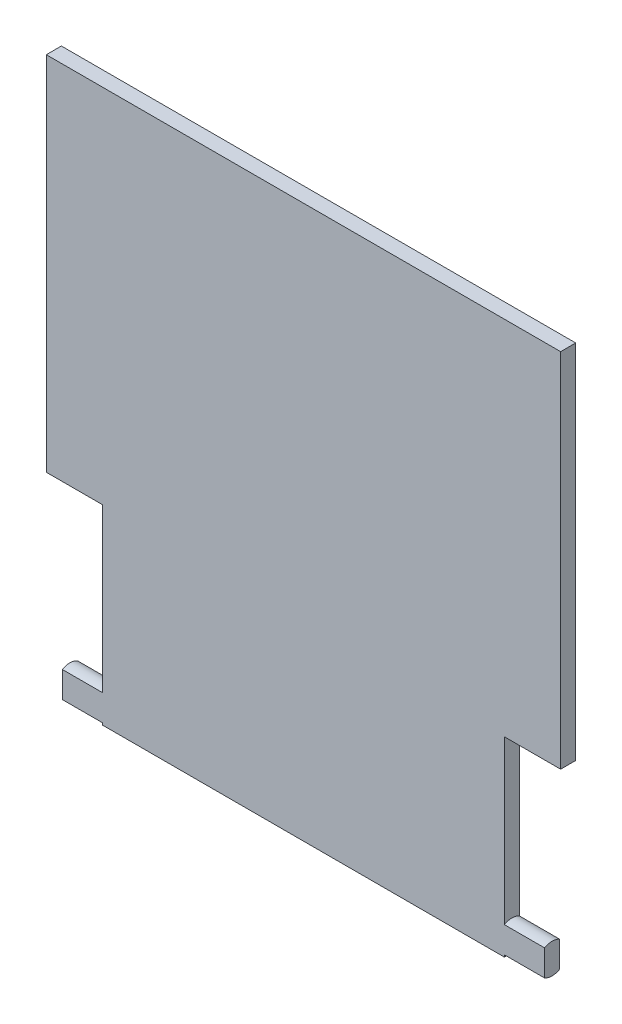
SolidWorks part; units mm, degrees
ref_plane "Front Plane" through (0, 0, 0) normal (0, 0, 1) x (1, 0, 0)
ref_plane "Top Plane" through (0, 0, 0) normal (0, 1, 0) x (1, 0, 0)
ref_plane "Right Plane" through (0, 0, 0) normal (1, 0, 0) x (0, 0, -1)
sketch "Sketch1" plane through (0, 0, 0) normal (0, 0, 1) x (1, 0, 0)
  line L0 (12, 0) -> (-12, 0)
  line L1 (-12, 0) -> (-12, 1.5)
  line L2 (-12, 1.5) -> (-10, 1.5)
  line L3 (-10, 1.5) -> (-10, 9.5)
  line L4 (-10, 9.5) -> (-12.8, 9.5)
  line L5 (-12.8, 9.5) -> (-12.8, 27.5)
  line L6 (-12.8, 27.5) -> (12.8, 27.5)
  line L7 (0, 2.4918) -> (0, -0.4688) construction
  line L8 (12.8, 9.5) -> (12.8, 27.5)
  line L9 (10, 9.5) -> (12.8, 9.5)
  line L10 (10, 1.5) -> (10, 9.5)
  line L11 (12, 1.5) -> (10, 1.5)
  line L12 (12, 0) -> (12, 1.5)
  point P12 (0, 27.5)
  point P17 (0, 0)
  dimension "D1" = 12
  dimension "D2" = 2
  dimension "D3" = 2.8
  dimension "D4" = 18
  dimension "D5" = 1.5
  dimension "D6" = 8
extrude "Boss-Extrude1" add sketch "Sketch1" along normal blind 0.75
sketch "Sketch2" plane through (-12, 0, 0) normal (-1, 0, 0) x (0, 0, 1)
  line L0 (0.375, 1.5) -> (0.375, 0) construction
  line L1 (0.75, 1.5) -> (0, 1.5) construction
  line L2 (0.75, 0) -> (0, 0) construction
  circle A0 centre (0.375, 0.75) radius 0.75
  circle A1 centre (0.375, 0.75) radius 1.5845
extrude "Cut-Extrude1" cut sketch "Sketch2" against normal up to surface (2 mm away) up to face at (-10, 5.5, 0.375)
sketch "Sketch3" plane through (12, 0, 0) normal (1, 0, 0) x (0, 0, -1)
  line L0 (-0.375, 1.5) -> (-0.375, 0) construction
  line L1 (-0.75, 1.5) -> (0, 1.5) construction
  circle A0 centre (-0.375, 0.75) radius 0.75
  circle A1 centre (-0.375, 0.75) radius 1.5645
extrude "Cut-Extrude2" cut sketch "Sketch3" against normal up to surface (2 mm away) up to face at (10, 5.5, 0.375)
